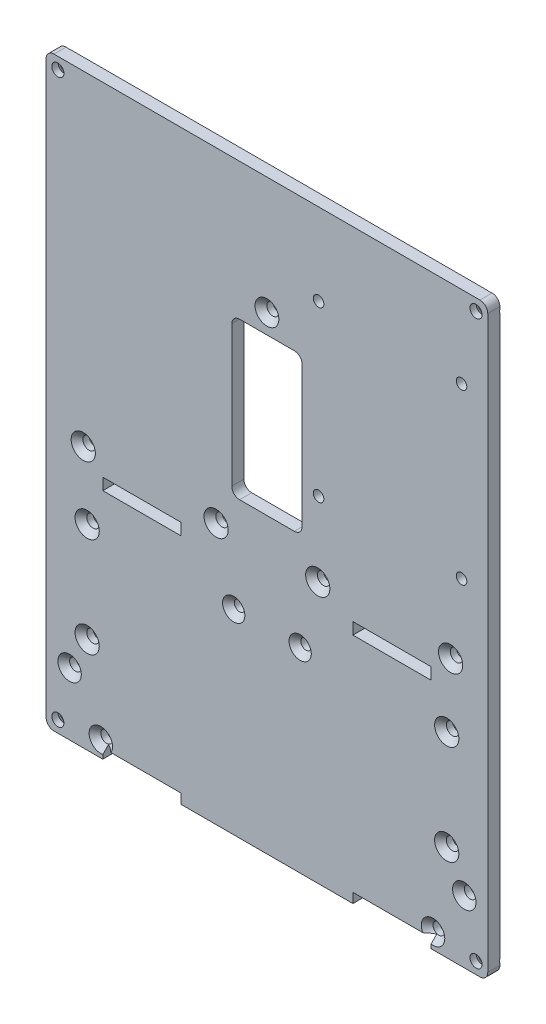
SolidWorks part; units mm, degrees
material "1023 Carbon Steel Sheet (SS)"
ref_plane "Front Plane" through (0, 0, 0) normal (0, 0, 1) x (1, 0, 0)
ref_plane "Top Plane" through (0, 0, 0) normal (0, 1, 0) x (1, 0, 0)
ref_plane "Right Plane" through (0, 0, 0) normal (1, 0, 0) x (0, 0, -1)
sketch "Sketch1" plane through (0, 0, 0) normal (0, 0, 1) x (1, 0, 0)
  line L1 (-56.5, 75) -> (56.5, 75)
  line L2 (-56.5, 75) -> (-56.5, -75)
  line L3 (-56.5, -75) -> (56.5, -75)
  line L4 (56.5, 75) -> (56.5, -75)
  line L5 (-56.5, 75) -> (56.5, -75) construction
  line L6 (-56.5, -75) -> (56.5, 75) construction
  point P0 (0, 0)
  dimension "D1" = 113
  dimension "D2" = 150
extrude "Boss-Extrude1" add sketch "Sketch1" along normal blind 3.1 contours L3 L4 L1 L2
sketch "Sketch3" plane through (0, 0, 3.1) normal (0, 0, 1) x (1, 0, 0)
  line L0 (-56.5, -75) -> (-30, -75)
  line L1 (-56.5, 75) -> (-56.5, -75) construction
  line L2 (-56.5, -75) -> (56.5, -75) construction
  line L3 (-30, -75) -> (-30, -8.2)
  line L4 (-47, -8.2) -> (-13, -8.2)
  line L5 (-42, -37.7) -> (-46, -37.7)
  line L6 (-30, -8.2) -> (-42, -8.2)
  line L7 (-30, -8.2) -> (-30, -37.7)
  line L8 (-30, -37.7) -> (-42, -37.7)
  line L10 (-46, -24.95) -> (-46, -50.45)
  circle A0 centre (-47, -8.2) radius 1.6
  circle A1 centre (-13, -8.2) radius 1.6
  circle A2 centre (-46, -24.95) radius 1.6
  circle A3 centre (-46, -50.45) radius 1.6
  point P10 (-30, -8.2)
  point P19 (-46, -37.7)
  dimension "D2" = 3.2
  dimension "D3" = 34
  dimension "D4" = 16
  dimension "D5" = 29.5
  dimension "D6" = 37.3
  dimension "D7" = 25.5
  dimension "D11" = 26.5
extrude "Cut-Extrude1" cut sketch "Sketch3" against normal blind 28 contours A1 | A0 | A2 | A3
mirror "Mirror1" about plane through (0, 0, 0) normal (1, 0, 0) of "Cut-Extrude1"
sketch "Sketch6" plane through (0, 0, 3.1) normal (0, 0, 1) x (1, 0, 0)
  line L0 (56.5, -75) -> (36.5, -75)
  line L1 (-56.5, -75) -> (56.5, -75) construction
  line L2 (36.5, -75) -> (36.5, -72.4)
  line L3 (36.5, -72.4) -> (-38.64, -72.4)
  line L4 (36.5, -72.4) -> (36.5, -24.14)
  line L5 (36.5, -24.14) -> (-14.3, -24.14)
  line L6 (-14.3, -24.14) -> (-14.3, -29.24)
  line L7 (-14.3, -24.14) -> (-44.78, -24.14)
  line L8 (36.5, -24.14) -> (37.77, -24.14)
  line L9 (-14.3, -29.24) -> (-14.3, -57.14)
  circle A0 centre (36.5, -72.4) radius 1.6
  circle A1 centre (-38.64, -72.4) radius 1.6
  circle A3 centre (-14.3, -29.24) radius 1.6
  circle A4 centre (-44.78, -24.14) radius 1.6
  circle A5 centre (37.77, -24.14) radius 1.6
  circle A6 centre (-14.3, -57.14) radius 1.6
  dimension "D3" = 3.2
  dimension "D5" = 3.2
  dimension "D7" = 1.27
  dimension "D10" = 3.2
  dimension "D12" = 3.2
  dimension "D13" = 3.2
  dimension "D15" = 3.2
  dimension "D1" = 20
  dimension "D2" = 2.6
  dimension "D4" = 75.14
  dimension "D6" = 48.26
  dimension "D8" = 50.8
  dimension "D9" = 5.1
  dimension "D11" = 30.48
  dimension "D14" = 27.9
extrude "Cut-Extrude4" [suppressed] cut sketch "Sketch6" against normal through all contours A3 | A0 | A1 | A5 | A6 | A4
sketch "Sketch7" plane through (0, 0, 3.1) normal (0, 0, 1) x (1, 0, 0)
  line L0 (-56.5, 75) -> (0, 75)
  line L1 (-56.5, 75) -> (56.5, 75) construction
  line L2 (0, 75) -> (0, -44)
  line L3 (0, -44) -> (-32, -44)
  line L4 (-32, -14) -> (-32, -74)
  line L5 (-42, -12.5) -> (-22, -12.5)
  line L6 (-42, -72.5) -> (-22, -72.5)
  line L7 (-42, -72.5) -> (-42, -75.5)
  line L8 (-42, -75.5) -> (-22, -75.5)
  line L9 (-22, -72.5) -> (-22, -75.5)
  line L10 (-42, -72.5) -> (-22, -75.5) construction
  line L11 (-42, -75.5) -> (-22, -72.5) construction
  line L12 (-22, -15.5) -> (-22, -12.5)
  line L13 (-42, -15.5) -> (-22, -15.5)
  line L14 (-42, -15.5) -> (-42, -12.5)
  line L15 (42, -75.5) -> (22, -75.5)
  line L16 (22, -72.5) -> (22, -75.5)
  line L17 (42, -72.5) -> (22, -72.5)
  line L18 (42, -72.5) -> (42, -75.5)
  line L19 (42, -15.5) -> (42, -12.5)
  line L20 (42, -15.5) -> (22, -15.5)
  line L21 (22, -15.5) -> (22, -12.5)
  line L22 (42, -12.5) -> (22, -12.5)
  point P10 (-32, -44)
  dimension "D1" = 56.5
  dimension "D2" = 119
  dimension "D3" = 60
  dimension "D4" = 3
  dimension "D5" = 20
  dimension "D6" = 32
extrude "Cut-Extrude5" cut sketch "Sketch7" against normal through all contours L12 L5 L14 L13 | L19 L22 L21 L20 | L18 L15 L16 L17 | L9 L8 L7 L6
sketch "Sketch8" plane through (0, 0, 3.1) normal (0, 0, 1) x (1, 0, 0)
  line L0 (-56.5, 75) -> (56.5, 75) construction
  line L1 (0, 75) -> (0, 45)
  circle A0 centre (0, 45) radius 1.55
  dimension "D2" = 3.1
  dimension "D1" = 30
extrude "Cut-Extrude6" cut sketch "Sketch8" against normal through all contours A0
sketch "Sketch9" plane through (0, 0, 3.1) normal (0, 0, 1) x (1, 0, 0)
  line L1 (-53.5, 72) -> (53.5, 72)
  line L2 (-53.5, 72) -> (-53.5, -72)
  line L3 (-53.5, -72) -> (53.5, -72)
  line L4 (53.5, 72) -> (53.5, -72)
  line L5 (-53.5, 72) -> (53.5, -72) construction
  line L6 (-53.5, -72) -> (53.5, 72) construction
  circle A0 centre (-53.5, 72) radius 1.55
  circle A1 centre (53.5, 72) radius 1.55
  circle A2 centre (53.5, -72) radius 1.55
  circle A3 centre (-53.5, -72) radius 1.55
  point P0 (0, 0)
  dimension "D3" = 3.1
  dimension "D1" = 107
  dimension "D2" = 144
extrude "Cut-Extrude7" cut sketch "Sketch9" against normal through all contours A0 | A1 | A2 | A3
sketch "Sketch10" plane through (0, 0, 3.1) normal (0, 0, 1) x (1, 0, 0)
  line L0 (-56.5, -75) -> (0, -75)
  line L2 (0, -75) -> (0, 20)
  line L4 (-9, 40) -> (9, 40)
  line L5 (-9, 40) -> (-9, 0)
  line L6 (-9, 0) -> (9, 0)
  line L7 (9, 40) -> (9, 0)
  line L8 (-9, 40) -> (9, 0) construction
  line L9 (-9, 0) -> (9, 40) construction
  dimension "D1" = 95
  dimension "D2" = 40
  dimension "D3" = 18
extrude "Cut-Extrude8" cut sketch "Sketch10" against normal through all contours L7 L6 L5 L4
fillet "Fillet1" radius 2 4 edges at (-9, 0, 1.55) (9, 0, 1.55) (9, 40, 1.55) (-9, 40, 1.55)
sketch "Sketch11" plane through (0, 0, 3.1) normal (0, 0, 1) x (1, 0, 0)
  line L0 (-56.5, -75) -> (0, -75)
  line L2 (0, -75) -> (0, -25)
  line L3 (-8.5, -25) -> (8.5, -25)
  circle A0 centre (-8.5, -25) radius 1.35
  circle A1 centre (8.5, -25) radius 1.35
  point P10 (0, -25)
  dimension "D3" = 2.7
  dimension "D1" = 50
  dimension "D2" = 17
extrude "Cut-Extrude9" cut sketch "Sketch11" against normal through all contours A1 | A0 region at (8.5, -23.6882, 3.1)
sketch "Sketch12" plane through (0, 0, 3.1) normal (0, 0, 1) x (1, 0, 0)
  line L0 (56.5, 75) -> (31.5, 75)
  line L1 (-56.5, 75) -> (56.5, 75) construction
  line L2 (31.5, 75) -> (31.5, 32.5)
  line L4 (13.21, 54.09) -> (49.79, 54.09)
  line L5 (13.21, 54.09) -> (13.21, 10.91)
  line L6 (13.21, 10.91) -> (49.79, 10.91)
  line L7 (49.79, 54.09) -> (49.79, 10.91)
  line L8 (13.21, 54.09) -> (49.79, 10.91) construction
  line L9 (13.21, 10.91) -> (49.79, 54.09) construction
  circle A0 centre (13.21, 54.09) radius 1.35
  circle A1 centre (49.79, 54.09) radius 1.35
  circle A2 centre (49.79, 10.91) radius 1.35
  circle A3 centre (13.21, 10.91) radius 1.35
  dimension "D5" = 2.7
  dimension "D1" = 25
  dimension "D2" = 42.5
  dimension "D3" = 43.18
  dimension "D4" = 36.58
extrude "Cytron" cut sketch "Sketch12" against normal through all contours A1 | A0 | A3 | A2
sketch "Sketch14" plane through (0, 0, 3.1) normal (0, 0, 1) x (1, 0, 0)
  line L0 (-56.5, -75) -> (-42.5, -75) construction
  line L1 (-56.5, -75) -> (-42, -75) construction
  line L2 (-42.5, -75) -> (-42.5, -59) construction
  line L3 (-42.5, -59) -> (-50.5, -59) construction
  circle A0 centre (-50.5, -59) radius 1.5
  circle A1 centre (-42.5, -71) radius 1.5
  dimension "D2" = 3
  dimension "D1" = 14
  dimension "D3" = 4
  dimension "D4" = 8
  dimension "D5" = 16
extrude "GuideMount" cut sketch "Sketch14" against normal through all contours A1 | A0 region at (-42.5, -71, 3.1)
mirror "Mirror2" about plane through (0, 0, 0) normal (1, 0, 0) of "GuideMount"
chamfer "Chamfer1" distance 1.5 angle 45 19 edges at (1.55, 45, 3.1) (11.4, -8.2, 3.1) (-11.4, -8.2, 3.1) (44.4, -50.45, 3.1) (44.4, -24.95, 3.1) (45.4, -8.2, 3.1) (-44.4, -50.45, 3.1) (-44.4, -24.95, 3.1) (-45.4, -8.2, 3.1) (9.85, -25, 3.1) (-7.15, -25, 3.1) (55.05, -72, 0) (55.05, 72, 0) (-51.95, 72, 0) (-51.95, -72, 0) (49, -59, 3.1) (41, -71, 3.1) (-49, -59, 3.1) (-41, -71, 3.1)
fillet "Fillet2" radius 2 4 edges at (56.5, -75, 1.55) (-56.5, -75, 1.55) (56.5, 75, 1.55) (-56.5, 75, 1.55)
